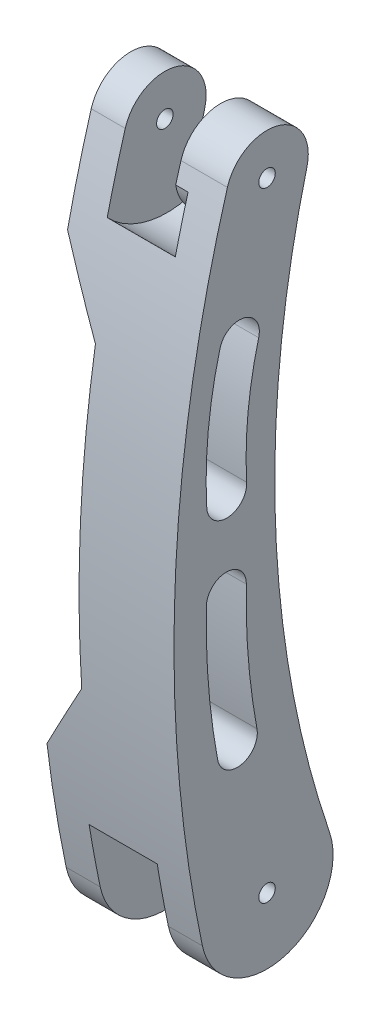
SolidWorks part; units mm, degrees
ref_plane "Plan de face" through (0, 0, 0) normal (0, 0, 1) x (1, 0, 0)
ref_plane "Plan de dessus" through (0, 0, 0) normal (0, 1, 0) x (1, 0, 0)
ref_plane "Plan de droite" through (0, 0, 0) normal (1, 0, 0) x (0, 0, -1)
sketch "Sketch1" plane through (0, 0, 0) normal (1, 0, 0) x (0, 0, -1)
  line L0 (0, 0) -> (0, 31.8922) construction
  line L1 (2.737, 64.8088) -> (-22.4583, 69.9701) construction
  line L2 (6.7932, 36.1883) -> (-21.1886, 33.337) construction
  line L3 (1.8824, 87.0744) -> (-21.408, 89.6176) construction
  line L4 (3.8165, 116.5957) -> (-17.2211, 120.8238) construction
  arc A0 (-15.6558, -3.3011) -> (15.1505, 5.1441) centre (0, 0) ccw
  arc A1 (9.6876, 147.52) -> (-9.5955, 152.8155) centre (0, 150) ccw
  circle A2 centre (0, 150) radius 2
  circle A3 centre (0, 0) radius 2
  arc A4 (-15.6558, -3.3011) -> (-9.5955, 152.8155) centre (297.4596, 62.72) cw
  arc A5 (9.6876, 147.52) -> (15.1505, 5.1441) centre (251.8776, 85.52) ccw
  arc A6 (-9.8606, 67.3895) -> (-7.1977, 34.7627) centre (150.2999, 64.0394) ccw construction
  arc A11 (-9.8606, 67.3895) -> (-7.1977, 34.7627) centre (150.2999, 64.0394) ccw construction
  arc A12 (-14.701, 67.4907) -> (-11.9575, 33.8779) centre (150.2999, 64.0394) ccw
  arc A13 (-5.0203, 67.2882) -> (-2.4379, 35.6475) centre (150.2999, 64.0394) ccw
  arc A14 (-5.0203, 67.2882) -> (-14.701, 67.4907) centre (-9.8606, 67.3895) ccw
  arc A15 (-11.9575, 33.8779) -> (-2.4379, 35.6475) centre (-7.1977, 34.7627) ccw
  arc A16 (-6.7023, 118.7098) -> (-9.7628, 88.346) centre (150.4307, 87.5357) ccw construction
  arc A17 (-6.7023, 118.7098) -> (-9.7628, 88.346) centre (88.4315, 93.7848) ccw construction
  arc A18 (-11.3856, 119.9368) -> (-14.5967, 88.0783) centre (88.4315, 93.7848) ccw
  arc A19 (-2.019, 117.4827) -> (-4.9288, 88.6138) centre (88.4315, 93.7848) ccw
  arc A20 (-2.019, 117.4827) -> (-11.3856, 119.9368) centre (-6.7023, 118.7098) ccw
  arc A21 (-14.5967, 88.0783) -> (-4.9288, 88.6138) centre (-9.7628, 88.346) ccw
  point P19 (-9.3648, 51.0079)
  point P33 (-9.4175, 103.6473)
  dimension "D4" = 20
  dimension "D5" = 320
  dimension "D6" = 250
  dimension "D1" = 16
  dimension "D2" = 150
  dimension "D3" = 32
  dimension "D7" = 35.5
extrude "Boss-Extrude1" add sketch "Sketch1" along normal blind 33
ref_plane "Plane1" through (8.25, 0, 0) normal (-1, 0, 0) x (0, 0, 1)
sketch "Sketch2" plane through (8.25, 0, 0) normal (-1, 0, 0) x (0, 0, 1)
  line L3 (0, 150) -> (0, 128.3969) construction
  arc A0 (9.5955, 152.8155) -> (-9.6876, 147.52) centre (0, 150) ccw construction
  arc A1 (9.5955, 152.8155) -> (-9.6876, 147.52) centre (0, 150) ccw
  arc A2 (15.6558, -3.3011) -> (9.5955, 152.8155) centre (-297.4596, 62.72) ccw construction
  arc A3 (-15.1505, 5.1441) -> (-9.6876, 147.52) centre (-251.8776, 85.52) ccw construction
  arc A4 (13.9698, 136.2845) -> (9.5955, 152.8155) centre (-297.4596, 62.72) ccw
  arc A5 (-6.0158, 130.8189) -> (-9.6876, 147.52) centre (-251.8776, 85.52) ccw
  arc A6 (13.9698, 136.2845) -> (-6.0158, 130.8189) centre (-0.5358, 150.0535) cw
  dimension "D3" = 20
  dimension "D1" = 17.1
  dimension "D2" = 17.1
extrude "Cut-Extrude1" cut sketch "Sketch2" against normal blind 13.5
sketch "Sketch3" plane through (8.25, 0, 0) normal (-1, 0, 0) x (0, 0, 1)
  line L0 (-4.2301, -15.4307) -> (5.2061, 21.3791) construction
  arc A0 (15.6558, -3.3011) -> (9.5955, 152.8155) centre (-297.4596, 62.72) ccw construction
  arc A1 (-15.1505, 5.1441) -> (-9.6876, 147.52) centre (-251.8776, 85.52) ccw construction
  arc A2 (-15.1505, 5.1441) -> (15.6558, -3.3011) centre (0, 0) ccw construction
  arc A3 (15.6558, -3.3011) -> (18.3548, 11.1323) centre (-297.4596, 62.72) ccw
  arc A4 (-15.1505, 5.1441) -> (-11.1389, 18.1043) centre (-251.8776, 85.52) ccw
  arc A5 (-15.1505, 5.1441) -> (15.6558, -3.3011) centre (0, 0) ccw
  arc A6 (-11.1389, 18.1043) -> (18.3548, 11.1323) centre (0.6051, 1.9155) cw
  dimension "D1" = 20
  dimension "D2" = 38
extrude "Cut-Extrude2" cut sketch "Sketch3" against normal blind 16.5
sketch "Sketch4" plane through (0, 0, 0) normal (-1, 0, 0) x (0, 0, 1)
  line L0 (5.5085, 3.4197) -> (6.2141, 16.8837)
  line L1 (1.1904, 17.9515) -> (-3.6413, 5.3646)
  circle A0 centre (0, 0) radius 2
  arc A1 (6.2141, 16.8837) -> (1.1904, 17.9515) centre (3.6177, 17.0198) ccw
  arc A2 (-3.8104, 5.1421) -> (-3.6413, 5.3646) centre (-4.1081, 5.5438) ccw
  arc A3 (-3.8104, 5.1421) -> (5.5725, 3.1477) centre (0, 0) ccw
  arc A4 (5.5085, 3.4197) -> (5.5725, 3.1477) centre (6.0078, 3.3936) ccw
extrude "Cut-Extrude3" cut sketch "Sketch4" against normal blind 5
sketch "Sketch6" plane through (21.75, 0, 0) normal (-1, 0, 0) x (0, 0, 1)
  circle A0 centre (0, 150) radius 2 construction
  arc A1 (-6.0158, 130.8189) -> (13.9698, 136.2845) centre (-0.5358, 150.0535) ccw construction
  arc A2 (-6.0158, 130.8189) -> (-9.6876, 147.52) centre (-251.8776, 85.52) ccw construction
  arc A3 (13.9698, 136.2845) -> (9.5955, 152.8155) centre (-297.4596, 62.72) ccw construction
  arc A4 (-6.0158, 130.8189) -> (-8.6124, 143.157) centre (-251.8776, 85.52) ccw
  arc A5 (13.9698, 136.2845) -> (10.8738, 148.3385) centre (-297.4596, 62.72) ccw
  arc A6 (-8.6124, 143.157) -> (10.8738, 148.3385) centre (0, 150) ccw
  arc A7 (15.6558, -3.3011) -> (9.5955, 152.8155) centre (-297.4596, 62.72) ccw construction
  arc A8 (-6.0158, 130.8189) -> (13.9698, 136.2845) centre (-0.5358, 150.0535) ccw
  circle A9 centre (0, 150) radius 2 construction
  dimension "D1" = 11
extrude "Cut-Extrude4" cut sketch "Sketch6" against normal blind 3
sketch "Sketch8" plane through (0, 0, 0) normal (0, 0, 1) x (1, 0, 0)
  line L0 (0, 152.8155) -> (0, -3.3011) construction
  line L1 (0, 130.2845) -> (0, 25)
  line L2 (0, 130.2845) -> (10, 112.9639)
  line L3 (10, 112.9639) -> (10, 42.3205)
  line L4 (10, 42.3205) -> (0, 25)
  line L6 (24.75, 136.2845) -> (8.25, 136.2845) construction
  dimension "D1" = 10
  dimension "D2" = 25
  dimension "D3" = 150
  dimension "D4" = 6
extrude "Cut-Extrude5" cut sketch "Sketch8" against normal through all both and the other way through all
equation "\"Longueur1\"= 150mm"
equation "\"Longueur2\"= 175mm"
equation "\"D2@Sketch1\"=\"Longueur1\""
equation "\"D2@Sketch2\"=\"D1@Sketch2\""
